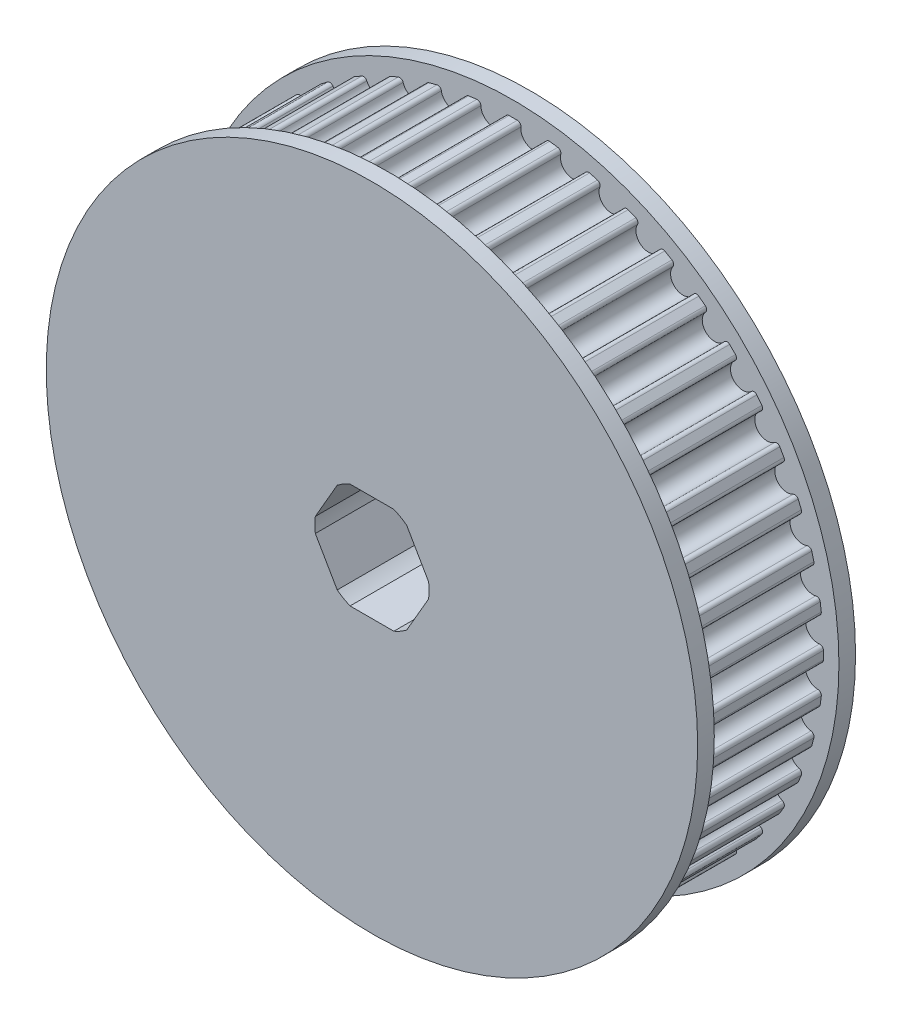
SolidWorks part; units mm, degrees
material "PE High Density"
ref_plane "Front Plane" through (0, 0, 0) normal (0, 0, 1) x (1, 0, 0)
ref_plane "Top Plane" through (0, 0, 0) normal (0, 1, 0) x (1, 0, 0)
ref_plane "Right Plane" through (0, 0, 0) normal (1, 0, 0) x (0, 0, -1)
sketch "Sketch2" plane through (0, 0, 0) normal (0, 0, 1) x (1, 0, 0)
  circle A0 centre (0, 0) radius 38.1972
  dimension "D1" = 76.3944
extrude "PD" add sketch "Sketch2" along normal mid plane 15
sketch "Sketch3" plane through (0, 0, 7.5) normal (0, 0, 1) x (1, 0, 0)
  line L0 (0, 0) -> (0, 37.3272) construction
  line L1 (0, 0) -> (2.404, 36.6785) construction
  line L2 (0, 37.3272) -> (0.4965, 37.3272)
  line L3 (0, 37.3272) -> (0, 38.1972)
  line L4 (4.8722, 37.0078) -> (4.9857, 37.8704)
  line L5 (4.8722, 37.0078) -> (4.3799, 37.0727)
  line L6 (2.404, 36.6785) -> (2.4982, 38.1154) construction
  arc A0 (0.4965, 37.3272) -> (0.9237, 36.8482) centre (0.4965, 36.8972) cw
  arc A1 (0.9237, 36.8482) -> (3.8938, 36.6535) centre (2.404, 36.6785) ccw
  circle A2 centre (0, 0) radius 38.1972 construction
  arc A3 (0, 38.1972) -> (4.9857, 37.8704) centre (0, 0) cw
  arc A4 (4.3799, 37.0727) -> (3.8938, 36.6535) centre (4.3238, 36.6463) ccw
  point P8 (2.3066, 35.1917)
  dimension "D1" = 0.43
  dimension "D2" = 1.49
  dimension "D3" = 0.87
  dimension "D4" = 3.75
  dimension "D5" = 2.93
extrude "Teeth" cut sketch "Sketch3" against normal up to surface (15 mm away) up to face at (38.1972, 0, -7.5)
pattern_circular "CirPattern1" count 48 over 360 about axis through (0, 0, 7.5) along (0, 0, 1) of "Teeth"
sketch "Sketch4" plane through (0, 0, 7.5) normal (0, 0, 1) x (1, 0, 0)
  circle A0 centre (0, 0) radius 39.1972
  dimension "D1" = 78.3944
extrude "Flange" add sketch "Sketch4" along normal blind 2
mirror "Flange 2" about plane through (0, 0, 0) normal (0, 0, 1) of "Flange"
sketch "Sketch6" plane through (0, 0, 0) normal (0, 0, 1) x (1, 0, 0)
  line L1 (6.8168, 0.893) -> (4.1818, 5.457)
  line L2 (2.635, 6.35) -> (-2.635, 6.35)
  line L3 (-4.1818, 5.457) -> (-6.8168, 0.893)
  line L4 (-6.8168, -0.893) -> (-4.1818, -5.457)
  line L5 (-2.635, -6.35) -> (2.635, -6.35)
  line L6 (4.1818, -5.457) -> (6.8168, -0.893)
  circle A0 centre (0, 0) radius 6.35 construction
  arc A1 (-2.635, 6.35) -> (-4.1818, 5.457) centre (0, 0) ccw
  arc A2 (-6.8168, 0.893) -> (-6.8168, -0.893) centre (0, 0) ccw
  arc A3 (-4.1818, -5.457) -> (-2.635, -6.35) centre (0, 0) ccw
  arc A4 (2.635, -6.35) -> (4.1818, -5.457) centre (0, 0) ccw
  arc A5 (6.8168, -0.893) -> (6.8168, 0.893) centre (0, 0) ccw
  arc A6 (4.1818, 5.457) -> (2.635, 6.35) centre (0, 0) ccw
  dimension "D2" = 13.75
  dimension "D1" = 12.7
extrude "Cut-Extrude2" cut sketch "Sketch6" against normal through all both and the other way through all
equation "\"D1@Sketch4\"= 16 + 2"
equation "\"D1@CirPattern1\" = 16"
equation "\"D4@Sketch3\" = 180 / 16"
equation "\"D1@Sketch2\" = 16 * 5 / pi"
